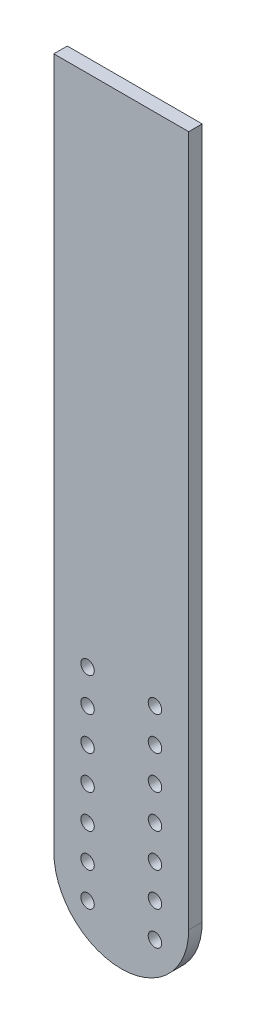
SolidWorks part; units mm, degrees
ref_plane "Front Plane" through (0, 0, 0) normal (0, 0, 1) x (1, 0, 0)
ref_plane "Top Plane" through (0, 0, 0) normal (0, 1, 0) x (1, 0, 0)
ref_plane "Right Plane" through (0, 0, 0) normal (1, 0, 0) x (0, 0, -1)
sketch "Sketch2" plane through (0, 0, 0) normal (0, 0, 1) x (1, 0, 0)
  line L1 (-20, 112.5) -> (20, 112.5)
  line L2 (-20, 112.5) -> (-20, -112.5)
  line L3 (-20, -112.5) -> (20, -112.5)
  line L4 (20, 112.5) -> (20, -112.5)
  line L5 (-20, 112.5) -> (20, -112.5) construction
  line L6 (-20, -112.5) -> (20, 112.5) construction
  point P0 (0, 0)
extrude "Boss-Extrude1" add sketch "Sketch2" along normal blind 4 contours L1 L4 L3 L2
sketch "Sketch3" plane through (0, 0, 4) normal (0, 0, 1) x (1, 0, 0)
  line L0 (-20, 112.5) -> (-20, -112.5) construction
  line L1 (-20, -112.5) -> (20, -112.5) construction
  line L2 (20, 112.5) -> (20, -112.5) construction
  circle A0 centre (-10, -100) radius 2
  circle A1 centre (10, -100) radius 2
  dimension "D1" = 10
  dimension "D2" = 12.5
  dimension "D3" = 10
  dimension "D4" = 12.5
extrude "Cut-Extrude1" cut sketch "Sketch3" against normal through all
pattern_linear "LPattern1" count 7 spacing 10 along (0, 1, 0) of "Cut-Extrude1"
fillet "Fillet2" radius 20 2 edges at (20, -112.5, 2) (-20, -112.5, 2)
